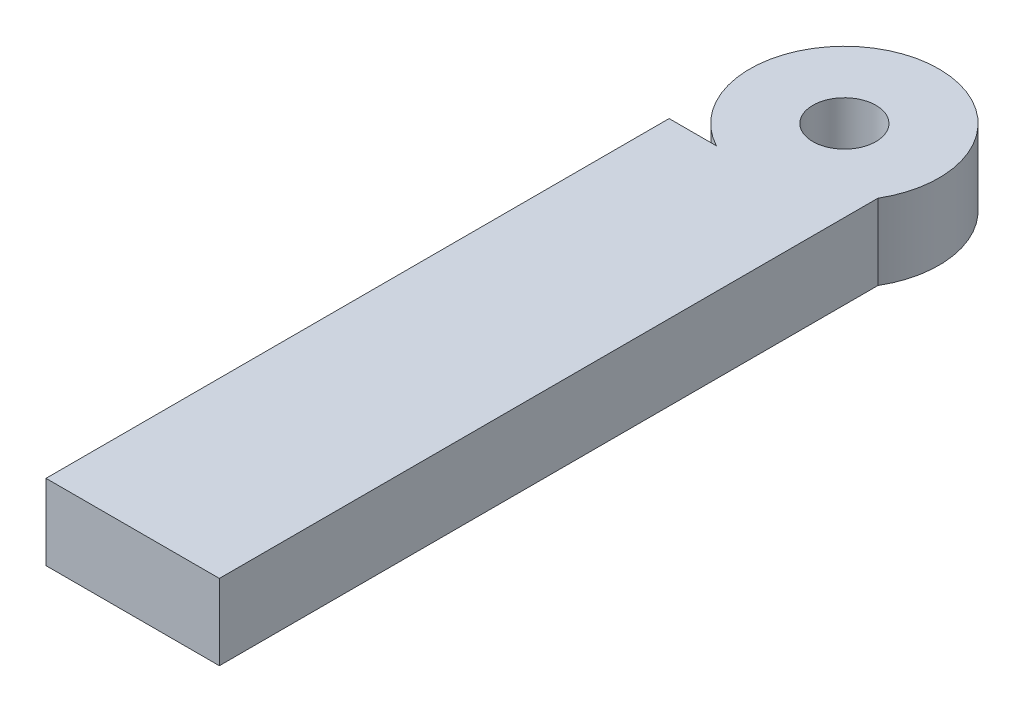
SolidWorks part; units mm, degrees
ref_plane "Front Plane" through (0, 0, 0) normal (0, 0, 1) x (1, 0, 0)
ref_plane "Top Plane" through (0, 0, 0) normal (0, 1, 0) x (1, 0, 0)
ref_plane "Right Plane" through (0, 0, 0) normal (1, 0, 0) x (0, 0, -1)
sketch "Sketch1" plane through (0, 0, 0) normal (0, 1, 0) x (1, 0, 0)
  line L0 (0, 9.525) -> (-4.4901, 5.0349)
  line L1 (0, 9.525) -> (0, 0) construction
  line L2 (-4.4901, -71.1651) -> (8.2099, -71.1651)
  line L3 (-4.4901, 5.0349) -> (-4.4901, -71.1651)
  line L4 (8.2099, -71.1651) -> (8.2099, -4.8295)
  circle A0 centre (0, 0) radius 3.175
  circle A1 centre (0, 0) radius 9.525
  dimension "D1" = 6.35
  dimension "D2" = 19.05
  dimension "D3" = 45
  dimension "D4" = 6.35
  dimension "D5" = 76.2
  dimension "D6" = 12.7
extrude "Boss-Extrude1" add sketch "Sketch1" along normal blind 7.62 region at (6.568, 0, -6.568) region at (-6.1109, 0, -0.9585) region at (1.9114, 0, 39.8268)
sketch "Sketch2" plane through (-4.4901, 0, 0) normal (-1, 0, 0) x (0, 0, 1)
  line L1 (8.4003, 7.62) -> (71.1651, 7.62) construction
  line L2 (8.4003, 7.62) -> (8.4003, 0) construction
  circle A0 centre (14.7503, 3.81) radius 2.54
  circle A1 centre (52.8503, 3.81) radius 2.54
  dimension "D1" = 5.08
  dimension "D2" = 5.08
  dimension "D3" = 6.35
  dimension "D4" = 3.81
  dimension "D5" = 38.1
extrude "Cut-Extrude1" cut sketch "Sketch2" against normal blind 6.35
sketch "Sketch3" [suppressed] plane through (-17.9605, 0, 0) normal (-1, 0, 0) x (0, 0, 1)
  line L4 (8.4355, 0) -> (59.2355, 0)
  line L5 (59.2355, 0) -> (59.2355, 7.62)
  line L6 (59.2355, 7.62) -> (8.4355, 7.62)
  line L7 (8.4355, 7.62) -> (8.4355, 0)
  line L8 (8.4355, 0) -> (59.2355, 0)
  line L9 (59.2355, 0) -> (59.2355, 7.62)
  line L10 (59.2355, 7.62) -> (8.4355, 7.62)
  line L11 (8.4355, 7.62) -> (8.4355, 0)
  circle A0 centre (52.8855, 3.81) radius 1.27 construction
  circle A1 centre (14.7855, 3.81) radius 1.27 construction
  circle A2 centre (52.8855, 3.81) radius 1.27
  circle A3 centre (14.7855, 3.81) radius 1.27
  dimension "D1" = 0
extrude "Boss-Extrude2" [suppressed] add sketch "Sketch3" along normal blind 9.525
sketch "Sketch4" plane through (-4.4901, 0, 0) normal (-1, 0, 0) x (0, 0, 1)
  line L4 (8.4003, 0) -> (71.1651, 0)
  line L5 (71.1651, 0) -> (71.1651, 7.62)
  line L6 (71.1651, 7.62) -> (8.4003, 7.62)
  line L7 (8.4003, 7.62) -> (8.4003, 0)
  line L8 (8.4003, 0) -> (71.1651, 0)
  line L9 (71.1651, 0) -> (71.1651, 7.62)
  line L10 (71.1651, 7.62) -> (8.4003, 7.62)
  line L12 (8.4003, 7.62) -> (8.4003, 0)
  circle A0 centre (52.8503, 3.81) radius 2.54 construction
  circle A1 centre (14.7503, 3.81) radius 2.54 construction
  circle A2 centre (52.8503, 3.81) radius 2.54
  circle A3 centre (14.7503, 3.81) radius 2.54
  dimension "D1" = 0
extrude "Boss-Extrude3" add sketch "Sketch4" along normal blind 4.7625
